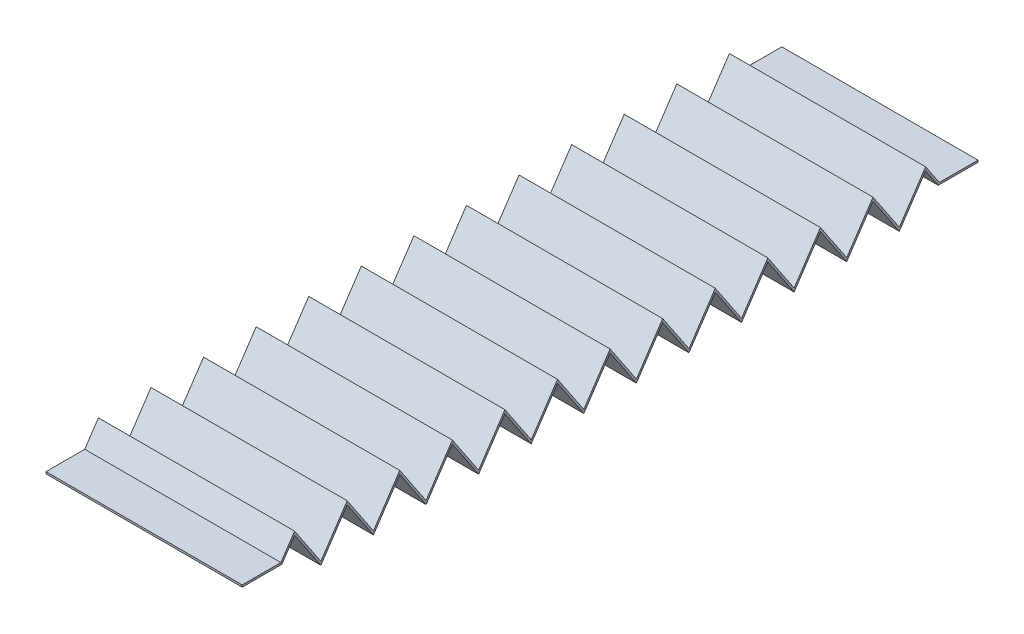
SolidWorks part; units mm, degrees
ref_plane "Front Plane" through (0, 0, 0) normal (0, 0, 1) x (1, 0, 0)
ref_plane "Top Plane" through (0, 0, 0) normal (0, 1, 0) x (1, 0, 0)
ref_plane "Right Plane" through (0, 0, 0) normal (1, 0, 0) x (0, 0, -1)
sketch "Sketch2" plane through (0, 0, 0) normal (0, 0, 1) x (1, 0, 0)
  line L1 (-27.5, 10) -> (27.5, 10)
  line L2 (-27.5, 10) -> (-27.5, 0)
  line L3 (-27.5, 0) -> (27.5, 0)
  line L4 (27.5, 10) -> (27.5, 0)
  point P4 (0, 0)
  dimension "D1" = 10
  dimension "D2" = 55
sketch "Sketch3" plane through (0, 0, 0) normal (1, 0, 0) x (0, 0, -1)
  line L0 (0, 10) -> (187.5006, 10) construction
  line L1 (0, 0) -> (187.5006, 0) construction
  line L3 (10, 5) -> (13.35, 10)
  line L4 (13.35, 10) -> (20.05, 0)
  line L5 (20.05, 0) -> (26.7501, 10)
  line L6 (26.7501, 10) -> (33.4501, 0)
  line L7 (33.4501, 0) -> (40.1501, 10)
  line L8 (40.1501, 10) -> (46.8501, 0)
  line L9 (46.8501, 0) -> (53.5502, 10)
  line L10 (53.5502, 10) -> (60.2502, 0)
  line L11 (60.2502, 0) -> (66.9502, 10)
  line L12 (66.9502, 10) -> (73.6502, 0)
  line L13 (73.6502, 0) -> (80.3503, 10)
  line L14 (80.3503, 10) -> (87.0503, 0)
  line L15 (87.0503, 0) -> (93.7503, 10)
  line L16 (93.7503, 10) -> (100.4503, 0)
  line L17 (100.4503, 0) -> (107.1503, 10)
  line L18 (107.1503, 10) -> (113.8504, 0)
  line L19 (0, 10) -> (0, 0) construction
  line L20 (113.8504, 0) -> (120.5504, 10)
  line L21 (120.5504, 10) -> (127.2504, 0)
  line L22 (127.2504, 0) -> (133.9504, 10)
  line L23 (133.9504, 10) -> (140.6505, 0)
  line L24 (140.6505, 0) -> (147.3505, 10)
  line L25 (147.3505, 10) -> (154.0505, 0)
  line L26 (154.0505, 0) -> (160.7505, 10)
  line L27 (160.7505, 10) -> (167.4506, 0)
  line L28 (167.4506, 0) -> (174.1506, 10)
  line L29 (174.1506, 10) -> (177.5006, 5)
  line L30 (187.5006, 10) -> (187.5006, 0) construction
  line L31 (10, 5) -> (0, 5)
  line L32 (177.5006, 5) -> (187.5006, 5)
  line L34 (187.5006, 22.75) -> (187.5006, 4.75) construction
  dimension "D2" = 10
  dimension "D1" = 10
  dimension "D3" = 10
extrude "Extrude-Thin1" add sketch "Sketch3" against normal mid plane 50 thin thin type mid plane wall 0.5
